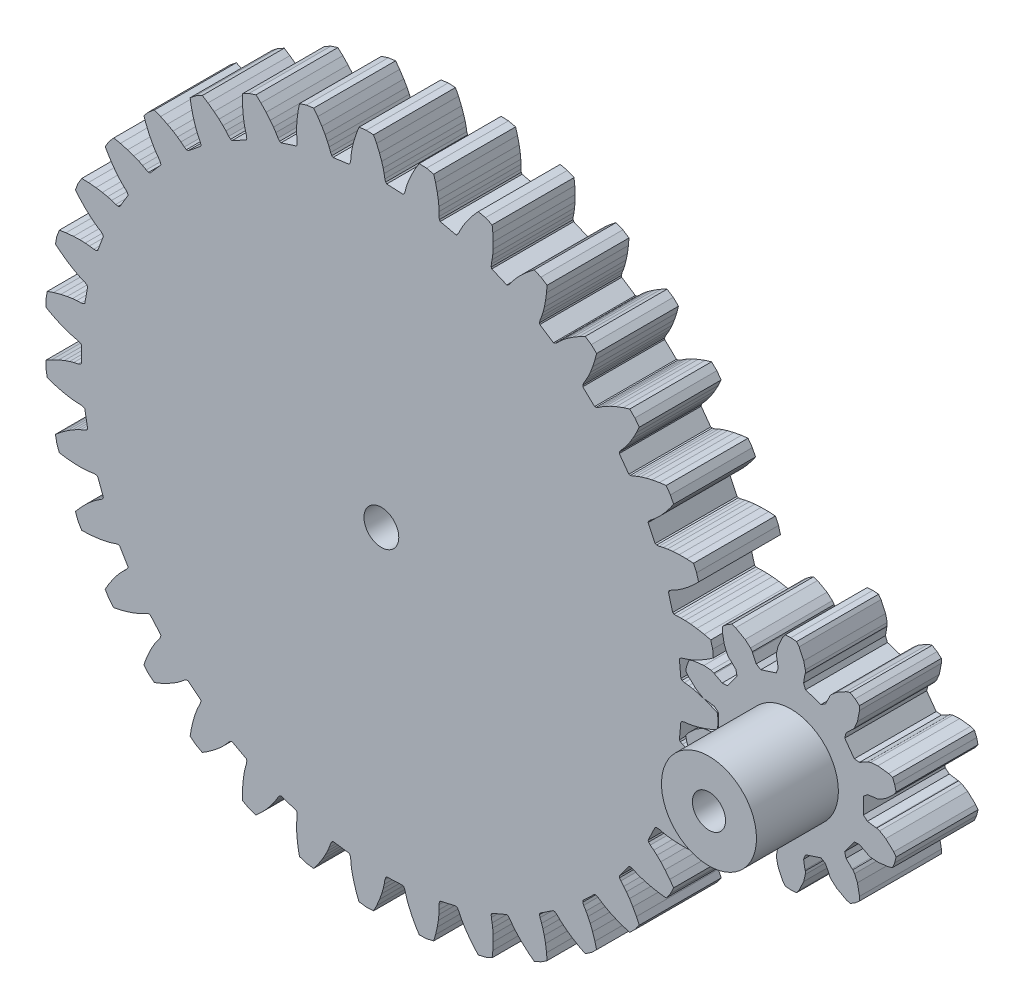
SolidWorks part; units mm, degrees
ref_plane "Front Plane" through (0, 0, 0) normal (0, 0, 1) x (1, 0, 0)
ref_plane "Top Plane" through (0, 0, 0) normal (0, 1, 0) x (1, 0, 0)
ref_plane "Right Plane" through (0, 0, 0) normal (1, 0, 0) x (0, 0, -1)
sketch "Sketch4" plane through (0, 0, 0) normal (0, 0, 1) x (1, 0, 0)
  line L0 (20.4281, -4.1664) -> (20.5488, -3.7291)
  line L1 (20.5488, -3.7291) -> (20.5895, -3.2772)
  line L2 (20.5895, -3.2772) -> (20.2452, -3.0423)
  line L3 (20.2452, -3.0423) -> (19.8455, -2.8032)
  line L4 (19.8455, -2.8032) -> (19.4917, -2.6194)
  line L5 (19.4917, -2.6194) -> (19.1886, -2.4843)
  line L6 (19.1886, -2.4843) -> (18.9407, -2.3911)
  line L7 (18.9407, -2.3911) -> (18.682, -2.3112)
  line L8 (18.682, -2.3112) -> (18.5457, -2.2427)
  line L9 (18.5457, -2.2427) -> (18.4844, -2.1704)
  line L10 (18.4844, -2.1704) -> (18.5748, -1.165)
  line L11 (18.5748, -1.165) -> (18.6481, -1.1048)
  line L12 (18.6481, -1.1048) -> (18.7945, -1.0617)
  line L13 (18.7945, -1.0617) -> (19.0633, -1.0293)
  line L14 (19.0633, -1.0293) -> (19.3238, -0.9819)
  line L15 (19.3238, -0.9819) -> (19.6461, -0.9031)
  line L16 (19.6461, -0.9031) -> (20.0271, -0.7854)
  line L17 (20.0271, -0.7854) -> (20.4631, -0.6215)
  line L18 (20.4631, -0.6215) -> (20.8438, -0.4518)
  line L19 (20.8438, -0.4518) -> (20.8844, 0)
  line L20 (20.8844, 0) -> (20.8438, 0.4518)
  line L21 (20.8438, 0.4518) -> (20.4631, 0.6215)
  line L22 (20.4631, 0.6215) -> (20.0271, 0.7854)
  line L23 (20.0271, 0.7854) -> (19.6461, 0.9031)
  line L24 (19.6461, 0.9031) -> (19.3238, 0.9819)
  line L25 (19.3238, 0.9819) -> (19.0633, 1.0293)
  line L26 (19.0633, 1.0293) -> (18.7945, 1.0617)
  line L27 (18.7945, 1.0617) -> (18.6481, 1.1048)
  line L28 (18.6481, 1.1048) -> (18.5748, 1.165)
  line L29 (18.5748, 1.165) -> (18.4844, 2.1704)
  line L30 (18.4844, 2.1704) -> (18.5457, 2.2427)
  line L31 (18.5457, 2.2427) -> (18.682, 2.3112)
  line L32 (18.682, 2.3112) -> (18.9407, 2.3911)
  line L33 (18.9407, 2.3911) -> (19.1886, 2.4843)
  line L34 (19.1886, 2.4843) -> (19.4917, 2.6194)
  line L35 (19.4917, 2.6194) -> (19.8455, 2.8032)
  line L36 (19.8455, 2.8032) -> (20.2452, 3.0423)
  line L37 (20.2452, 3.0423) -> (20.5895, 3.2772)
  line L38 (20.5895, 3.2772) -> (20.5488, 3.7291)
  line L39 (20.5488, 3.7291) -> (20.4281, 4.1664)
  line L40 (20.4281, 4.1664) -> (20.0232, 4.2654)
  line L41 (20.0232, 4.2654) -> (19.565, 4.3487)
  line L42 (19.565, 4.3487) -> (19.1692, 4.3965)
  line L43 (19.1692, 4.3965) -> (18.838, 4.4165)
  line L44 (18.838, 4.4165) -> (18.5731, 4.4166)
  line L45 (18.5731, 4.4166) -> (18.3029, 4.4005)
  line L46 (18.3029, 4.4005) -> (18.1512, 4.4168)
  line L47 (18.1512, 4.4168) -> (18.0683, 4.4629)
  line L48 (18.0683, 4.4629) -> (17.7998, 5.436)
  line L49 (17.7998, 5.436) -> (17.8472, 5.5181)
  line L50 (17.8472, 5.5181) -> (17.9691, 5.6099)
  line L51 (17.9691, 5.6099) -> (18.2093, 5.7347)
  line L52 (18.2093, 5.7347) -> (18.4366, 5.8706)
  line L53 (18.4366, 5.8706) -> (18.7107, 6.0577)
  line L54 (18.7107, 6.0577) -> (19.026, 6.3017)
  line L55 (19.026, 6.3017) -> (19.3766, 6.6083)
  line L56 (19.3766, 6.6083) -> (19.6734, 6.9009)
  line L57 (19.6734, 6.9009) -> (19.5527, 7.3383)
  line L58 (19.5527, 7.3383) -> (19.3559, 7.747)
  line L59 (19.3559, 7.747) -> (18.9398, 7.7721)
  line L60 (18.9398, 7.7721) -> (18.4741, 7.7723)
  line L61 (18.4741, 7.7723) -> (18.0761, 7.7486)
  line L62 (18.0761, 7.7486) -> (17.7466, 7.7092)
  line L63 (17.7466, 7.7092) -> (17.486, 7.662)
  line L64 (17.486, 7.662) -> (17.223, 7.5979)
  line L65 (17.223, 7.5979) -> (17.0708, 7.5868)
  line L66 (17.0708, 7.5868) -> (16.9811, 7.6174)
  line L67 (16.9811, 7.6174) -> (16.5431, 8.5269)
  line L68 (16.5431, 8.5269) -> (16.5751, 8.6162)
  line L69 (16.5751, 8.6162) -> (16.6786, 8.7282)
  line L70 (16.6786, 8.7282) -> (16.8927, 8.894)
  line L71 (16.8927, 8.894) -> (17.0921, 9.0683)
  line L72 (17.0921, 9.0683) -> (17.3284, 9.3012)
  line L73 (17.3284, 9.3012) -> (17.5951, 9.5977)
  line L74 (17.5951, 9.5977) -> (17.8853, 9.9619)
  line L75 (17.8853, 9.9619) -> (18.1251, 10.3029)
  line L76 (18.1251, 10.3029) -> (17.9282, 10.7116)
  line L77 (17.9282, 10.7116) -> (17.6616, 11.0786)
  line L78 (17.6616, 11.0786) -> (17.2477, 11.0291)
  line L79 (17.2477, 11.0291) -> (16.7894, 10.9461)
  line L80 (16.7894, 10.9461) -> (16.402, 10.8517)
  line L81 (16.402, 10.8517) -> (16.0849, 10.7541)
  line L82 (16.0849, 10.7541) -> (15.8369, 10.6611)
  line L83 (15.8369, 10.6611) -> (15.5895, 10.5511)
  line L84 (15.5895, 10.5511) -> (15.4418, 10.513)
  line L85 (15.4418, 10.513) -> (15.348, 10.5271)
  line L86 (15.348, 10.5271) -> (14.7547, 11.3438)
  line L87 (14.7547, 11.3438) -> (14.7703, 11.4373)
  line L88 (14.7703, 11.4373) -> (14.8521, 11.5661)
  line L89 (14.8521, 11.5661) -> (15.0332, 11.7673)
  line L90 (15.0332, 11.7673) -> (15.1982, 11.9745)
  line L91 (15.1982, 11.9745) -> (15.3891, 12.2459)
  line L92 (15.3891, 12.2459) -> (15.5986, 12.5852)
  line L93 (15.5986, 12.5852) -> (15.8191, 12.9954)
  line L94 (15.8191, 12.9954) -> (15.9941, 13.3737)
  line L95 (15.9941, 13.3737) -> (15.7275, 13.7407)
  line L96 (15.7275, 13.7407) -> (15.3996, 14.0542)
  line L97 (15.3996, 14.0542) -> (15.0012, 13.9315)
  line L98 (15.0012, 13.9315) -> (14.5651, 13.7681)
  line L99 (14.5651, 13.7681) -> (14.2008, 13.606)
  line L100 (14.2008, 13.606) -> (13.9062, 13.4533)
  line L101 (13.9062, 13.4533) -> (13.6788, 13.3176)
  line L102 (13.6788, 13.3176) -> (13.455, 13.1652)
  line L103 (13.455, 13.1652) -> (13.3165, 13.1013)
  line L104 (13.3165, 13.1013) -> (13.2217, 13.0984)
  line L105 (13.2217, 13.0984) -> (12.4921, 13.796)
  line L106 (12.4921, 13.796) -> (12.4907, 13.8909)
  line L107 (12.4907, 13.8909) -> (12.5482, 14.0321)
  line L108 (12.5482, 14.0321) -> (12.6905, 14.2625)
  line L109 (12.6905, 14.2625) -> (12.8159, 14.4958)
  line L110 (12.8159, 14.4958) -> (12.9552, 14.7969)
  line L111 (12.9552, 14.7969) -> (13.1007, 15.1682)
  line L112 (13.1007, 15.1682) -> (13.2445, 15.6111)
  line L113 (13.2445, 15.6111) -> (13.3491, 16.0146)
  line L114 (13.3491, 16.0146) -> (13.0212, 16.3281)
  line L115 (13.0212, 16.3281) -> (12.6426, 16.578)
  line L116 (12.6426, 16.578) -> (12.2726, 16.3862)
  line L117 (12.2726, 16.3862) -> (11.8727, 16.1475)
  line L118 (11.8727, 16.1475) -> (11.5431, 15.923)
  line L119 (11.5431, 15.923) -> (11.2805, 15.7202)
  line L120 (11.2805, 15.7202) -> (11.081, 15.546)
  line L121 (11.081, 15.546) -> (10.8881, 15.3561)
  line L122 (10.8881, 15.3561) -> (10.7632, 15.2685)
  line L123 (10.7632, 15.2685) -> (10.6704, 15.2488)
  line L124 (10.6704, 15.2488) -> (9.8279, 15.8049)
  line L125 (9.8279, 15.8049) -> (9.8096, 15.8979)
  line L126 (9.8096, 15.8979) -> (9.841, 16.0472)
  line L127 (9.841, 16.0472) -> (9.9399, 16.2993)
  line L128 (9.9399, 16.2993) -> (10.0216, 16.5512)
  line L129 (10.0216, 16.5512) -> (10.1049, 16.8724)
  line L130 (10.1049, 16.8724) -> (10.1818, 17.2636)
  line L131 (10.1818, 17.2636) -> (10.2441, 17.7251)
  line L132 (10.2441, 17.7251) -> (10.2751, 18.1408)
  line L133 (10.2751, 18.1408) -> (9.8965, 18.3907)
  line L134 (9.8965, 18.3907) -> (9.4793, 18.5691)
  line L135 (9.4793, 18.5691) -> (9.1495, 18.3142)
  line L136 (9.1495, 18.3142) -> (8.7986, 18.008)
  line L137 (8.7986, 18.008) -> (8.5144, 17.7282)
  line L138 (8.5144, 17.7282) -> (8.2923, 17.4817)
  line L139 (8.2923, 17.4817) -> (8.1271, 17.2748)
  line L140 (8.1271, 17.2748) -> (7.9712, 17.0534)
  line L141 (7.9712, 17.0534) -> (7.8639, 16.945)
  line L142 (7.8639, 16.945) -> (7.7762, 16.909)
  line L143 (7.7762, 16.909) -> (6.8479, 17.3057)
  line L144 (6.8479, 17.3057) -> (6.8133, 17.394)
  line L145 (6.8133, 17.394) -> (6.8176, 17.5465)
  line L146 (6.8176, 17.5465) -> (6.8698, 17.8122)
  line L147 (6.8698, 17.8122) -> (6.9052, 18.0746)
  line L148 (6.9052, 18.0746) -> (6.9299, 18.4055)
  line L149 (6.9299, 18.4055) -> (6.9357, 18.8042)
  line L150 (6.9357, 18.8042) -> (6.9146, 19.2695)
  line L151 (6.9146, 19.2695) -> (6.8708, 19.684)
  line L152 (6.8708, 19.684) -> (6.4536, 19.8623)
  line L153 (6.4536, 19.8623) -> (6.0114, 19.9632)
  line L154 (6.0114, 19.9632) -> (5.7323, 19.6536)
  line L155 (5.7323, 19.6536) -> (5.4418, 19.2896)
  line L156 (5.4418, 19.2896) -> (5.2121, 18.9636)
  line L157 (5.2121, 18.9636) -> (5.0376, 18.6815)
  line L158 (5.0376, 18.6815) -> (4.912, 18.4483)
  line L159 (4.912, 18.4483) -> (4.7981, 18.2027)
  line L160 (4.7981, 18.2027) -> (4.7119, 18.0768)
  line L161 (4.7119, 18.0768) -> (4.632, 18.0257)
  line L162 (4.632, 18.0257) -> (3.6478, 18.2504)
  line L163 (3.6478, 18.2504) -> (3.598, 18.3311)
  line L164 (3.598, 18.3311) -> (3.5749, 18.4819)
  line L165 (3.5749, 18.4819) -> (3.5789, 18.7526)
  line L166 (3.5789, 18.7526) -> (3.5669, 19.0171)
  line L167 (3.5669, 19.0171) -> (3.5321, 19.3471)
  line L168 (3.5321, 19.3471) -> (3.4666, 19.7404)
  line L169 (3.4666, 19.7404) -> (3.3627, 20.1944)
  line L170 (3.3627, 20.1944) -> (3.2457, 20.5945)
  line L171 (3.2457, 20.5945) -> (2.8034, 20.6954)
  line L172 (2.8034, 20.6954) -> (2.3502, 20.7158)
  line L173 (2.3502, 20.7158) -> (2.1309, 20.3613)
  line L174 (2.1309, 20.3613) -> (1.91, 19.9513)
  line L175 (1.91, 19.9513) -> (1.7423, 19.5895)
  line L176 (1.7423, 19.5895) -> (1.6209, 19.2807)
  line L177 (1.6209, 19.2807) -> (1.539, 19.0289)
  line L178 (1.539, 19.0289) -> (1.4707, 18.7669)
  line L179 (1.4707, 18.7669) -> (1.4084, 18.6277)
  line L180 (1.4084, 18.6277) -> (1.3389, 18.5631)
  line L181 (1.3389, 18.5631) -> (0.3305, 18.6084)
  line L182 (0.3305, 18.6084) -> (0.267, 18.6789)
  line L183 (0.267, 18.6789) -> (0.2174, 18.8232)
  line L184 (0.2174, 18.8232) -> (0.173, 19.0902)
  line L185 (0.173, 19.0902) -> (0.1139, 19.3484)
  line L186 (0.1139, 19.3484) -> (0.0207, 19.6669)
  line L187 (0.0207, 19.6669) -> (-0.1139, 20.0422)
  line L188 (-0.1139, 20.0422) -> (-0.2972, 20.4703)
  line L189 (-0.2972, 20.4703) -> (-0.4838, 20.8431)
  line L190 (-0.4838, 20.8431) -> (-0.937, 20.8634)
  line L191 (-0.937, 20.8634) -> (-1.3865, 20.8025)
  line L192 (-1.3865, 20.8025) -> (-1.539, 20.4146)
  line L193 (-1.539, 20.4146) -> (-1.6831, 19.9717)
  line L194 (-1.6831, 19.9717) -> (-1.7836, 19.5858)
  line L195 (-1.7836, 19.5858) -> (-1.8478, 19.2603)
  line L196 (-1.8478, 19.2603) -> (-1.8835, 18.9979)
  line L197 (-1.8835, 18.9979) -> (-1.9039, 18.7279)
  line L198 (-1.9039, 18.7279) -> (-1.9403, 18.5798)
  line L199 (-1.9403, 18.5798) -> (-1.9972, 18.5039)
  line L200 (-1.9972, 18.5039) -> (-2.9975, 18.3684)
  line L201 (-2.9975, 18.3684) -> (-3.0725, 18.4264)
  line L202 (-3.0725, 18.4264) -> (-3.1471, 18.5595)
  line L203 (-3.1471, 18.5595) -> (-3.2385, 18.8143)
  line L204 (-3.2385, 18.8143) -> (-3.3427, 19.0578)
  line L205 (-3.3427, 19.0578) -> (-3.4912, 19.3545)
  line L206 (-3.4912, 19.3545) -> (-3.6908, 19.6998)
  line L207 (-3.6908, 19.6998) -> (-3.9475, 20.0883)
  line L208 (-3.9475, 20.0883) -> (-4.1977, 20.4217)
  line L209 (-4.1977, 20.4217) -> (-4.6472, 20.3608)
  line L210 (-4.6472, 20.3608) -> (-5.0787, 20.2206)
  line L211 (-5.0787, 20.2206) -> (-5.1594, 19.8117)
  line L212 (-5.1594, 19.8117) -> (-5.2221, 19.3502)
  line L213 (-5.2221, 19.3502) -> (-5.2521, 18.9526)
  line L214 (-5.2521, 18.9526) -> (-5.2572, 18.6208)
  line L215 (-5.2572, 18.6208) -> (-5.2454, 18.3563)
  line L216 (-5.2454, 18.3563) -> (-5.2173, 18.087)
  line L217 (-5.2173, 18.087) -> (-5.2267, 17.9347)
  line L218 (-5.2267, 17.9347) -> (-5.2691, 17.8499)
  line L219 (-5.2691, 17.8499) -> (-6.2291, 17.538)
  line L220 (-6.2291, 17.538) -> (-6.3133, 17.5817)
  line L221 (-6.3133, 17.5817) -> (-6.4104, 17.6993)
  line L222 (-6.4104, 17.6993) -> (-6.5459, 17.9337)
  line L223 (-6.5459, 17.9337) -> (-6.6919, 18.1547)
  line L224 (-6.6919, 18.1547) -> (-6.891, 18.4201)
  line L225 (-6.891, 18.4201) -> (-7.149, 18.7242)
  line L226 (-7.149, 18.7242) -> (-7.471, 19.0606)
  line L227 (-7.471, 19.0606) -> (-7.7766, 19.344)
  line L228 (-7.7766, 19.344) -> (-8.2081, 19.2038)
  line L229 (-8.2081, 19.2038) -> (-8.6076, 18.9888)
  line L230 (-8.6076, 18.9888) -> (-8.614, 18.5721)
  line L231 (-8.614, 18.5721) -> (-8.5933, 18.1068)
  line L232 (-8.5933, 18.1068) -> (-8.5518, 17.7102)
  line L233 (-8.5518, 17.7102) -> (-8.4976, 17.3829)
  line L234 (-8.4976, 17.3829) -> (-8.4388, 17.1247)
  line L235 (-8.4388, 17.1247) -> (-8.363, 16.8648)
  line L236 (-8.363, 16.8648) -> (-8.3451, 16.7133)
  line L237 (-8.3451, 16.7133) -> (-8.3716, 16.6222)
  line L238 (-8.3716, 16.6222) -> (-9.2606, 16.1439)
  line L239 (-9.2606, 16.1439) -> (-9.3512, 16.1719)
  line L240 (-9.3512, 16.1719) -> (-9.4677, 16.2703)
  line L241 (-9.4677, 16.2703) -> (-9.6429, 16.4767)
  line L242 (-9.6429, 16.4767) -> (-9.826, 16.6681)
  line L243 (-9.826, 16.6681) -> (-10.0693, 16.8936)
  line L244 (-10.0693, 16.8936) -> (-10.3774, 17.1468)
  line L245 (-10.3774, 17.1468) -> (-10.7543, 17.4203)
  line L246 (-10.7543, 17.4203) -> (-11.1057, 17.6446)
  line L247 (-11.1057, 17.6446) -> (-11.5052, 17.4296)
  line L248 (-11.5052, 17.4296) -> (-11.8599, 17.1467)
  line L249 (-11.8599, 17.1467) -> (-11.7918, 16.7355)
  line L250 (-11.7918, 16.7355) -> (-11.6883, 16.2814)
  line L251 (-11.6883, 16.2814) -> (-11.5767, 15.8986)
  line L252 (-11.5767, 15.8986) -> (-11.4649, 15.5862)
  line L253 (-11.4649, 15.5862) -> (-11.3609, 15.3427)
  line L254 (-11.3609, 15.3427) -> (-11.2399, 15.1005)
  line L255 (-11.2399, 15.1005) -> (-11.1952, 14.9546)
  line L256 (-11.1952, 14.9546) -> (-11.2051, 14.8603)
  line L257 (-11.2051, 14.8603) -> (-11.9943, 14.2309)
  line L258 (-11.9943, 14.2309) -> (-12.0885, 14.2422)
  line L259 (-12.0885, 14.2422) -> (-12.2208, 14.3183)
  line L260 (-12.2208, 14.3183) -> (-12.43, 14.4901)
  line L261 (-12.43, 14.4901) -> (-12.6443, 14.6457)
  line L262 (-12.6443, 14.6457) -> (-12.924, 14.8242)
  line L263 (-12.924, 14.8242) -> (-13.2723, 15.0182)
  line L264 (-13.2723, 15.0182) -> (-13.692, 15.2201)
  line L265 (-13.692, 15.2201) -> (-14.0778, 15.378)
  line L266 (-14.0778, 15.378) -> (-14.4325, 15.0952)
  line L267 (-14.4325, 15.0952) -> (-14.7309, 14.7535)
  line L268 (-14.7309, 14.7535) -> (-14.5905, 14.3611)
  line L269 (-14.5905, 14.3611) -> (-14.4077, 13.9328)
  line L270 (-14.4077, 13.9328) -> (-14.2294, 13.576)
  line L271 (-14.2294, 13.576) -> (-14.0637, 13.2886)
  line L272 (-14.0637, 13.2886) -> (-13.9179, 13.0675)
  line L273 (-13.9179, 13.0675) -> (-13.7556, 12.8508)
  line L274 (-13.7556, 12.8508) -> (-13.6856, 12.7153)
  line L275 (-13.6856, 12.7153) -> (-13.6784, 12.6207)
  line L276 (-13.6784, 12.6207) -> (-14.3426, 11.8605)
  line L277 (-14.3426, 11.8605) -> (-14.4373, 11.8549)
  line L278 (-14.4373, 11.8549) -> (-14.581, 11.9061)
  line L279 (-14.581, 11.9061) -> (-14.8175, 12.0378)
  line L280 (-14.8175, 12.0378) -> (-15.0562, 12.1526)
  line L281 (-15.0562, 12.1526) -> (-15.3632, 12.2783)
  line L282 (-15.3632, 12.2783) -> (-15.7406, 12.407)
  line L283 (-15.7406, 12.407) -> (-16.1896, 12.5307)
  line L284 (-16.1896, 12.5307) -> (-16.5974, 12.6172)
  line L285 (-16.5974, 12.6172) -> (-16.8959, 12.2756)
  line L286 (-16.8959, 12.2756) -> (-17.1286, 11.8861)
  line L287 (-17.1286, 11.8861) -> (-16.9203, 11.525)
  line L288 (-16.9203, 11.525) -> (-16.6639, 11.1363)
  line L289 (-16.6639, 11.1363) -> (-16.4249, 10.8171)
  line L290 (-16.4249, 10.8171) -> (-16.2104, 10.5639)
  line L291 (-16.2104, 10.5639) -> (-16.0275, 10.3724)
  line L292 (-16.0275, 10.3724) -> (-15.8291, 10.1882)
  line L293 (-15.8291, 10.1882) -> (-15.736, 10.0673)
  line L294 (-15.736, 10.0673) -> (-15.7121, 9.9755)
  line L295 (-15.7121, 9.9755) -> (-16.2299, 9.1089)
  line L296 (-16.2299, 9.1089) -> (-16.322, 9.0865)
  line L297 (-16.322, 9.0865) -> (-16.4726, 9.1112)
  line L298 (-16.4726, 9.1112) -> (-16.7288, 9.1986)
  line L299 (-16.7288, 9.1986) -> (-16.9841, 9.2689)
  line L300 (-16.9841, 9.2689) -> (-17.3087, 9.3378)
  line L301 (-17.3087, 9.3378) -> (-17.703, 9.397)
  line L302 (-17.703, 9.397) -> (-18.1669, 9.4386)
  line L303 (-18.1669, 9.4386) -> (-18.5835, 9.4509)
  line L304 (-18.5835, 9.4509) -> (-18.8162, 9.0614)
  line L305 (-18.8162, 9.0614) -> (-18.9756, 8.6367)
  line L306 (-18.9756, 8.6367) -> (-18.7063, 8.3186)
  line L307 (-18.7063, 8.3186) -> (-18.3846, 7.9818)
  line L308 (-18.3846, 7.9818) -> (-18.0924, 7.7105)
  line L309 (-18.0924, 7.7105) -> (-17.8362, 7.4997)
  line L310 (-17.8362, 7.4997) -> (-17.622, 7.3439)
  line L311 (-17.622, 7.3439) -> (-17.3939, 7.198)
  line L312 (-17.3939, 7.198) -> (-17.2807, 7.0957)
  line L313 (-17.2807, 7.0957) -> (-17.2408, 7.0097)
  line L314 (-17.2408, 7.0097) -> (-17.5955, 6.0646)
  line L315 (-17.5955, 6.0646) -> (-17.6822, 6.0261)
  line L316 (-17.6822, 6.0261) -> (-17.8347, 6.0235)
  line L317 (-17.8347, 6.0235) -> (-18.1024, 6.0637)
  line L318 (-18.1024, 6.0637) -> (-18.3662, 6.0873)
  line L319 (-18.3662, 6.0873) -> (-18.6979, 6.0971)
  line L320 (-18.6979, 6.0971) -> (-19.0965, 6.085)
  line L321 (-19.0965, 6.085) -> (-19.5603, 6.0431)
  line L322 (-19.5603, 6.0431) -> (-19.9724, 5.9808)
  line L323 (-19.9724, 5.9808) -> (-20.1318, 5.556)
  line L324 (-20.1318, 5.556) -> (-20.2128, 5.1097)
  line L325 (-20.2128, 5.1097) -> (-19.891, 4.8448)
  line L326 (-19.891, 4.8448) -> (-19.5143, 4.5709)
  line L327 (-19.5143, 4.5709) -> (-19.1784, 4.3561)
  line L328 (-19.1784, 4.3561) -> (-18.8887, 4.1944)
  line L329 (-18.8887, 4.1944) -> (-18.6501, 4.0793)
  line L330 (-18.6501, 4.0793) -> (-18.3996, 3.9766)
  line L331 (-18.3996, 3.9766) -> (-18.27, 3.8961)
  line L332 (-18.27, 3.8961) -> (-18.2154, 3.8186)
  line L333 (-18.2154, 3.8186) -> (-18.3956, 2.8253)
  line L334 (-18.3956, 2.8253) -> (-18.474, 2.7719)
  line L335 (-18.474, 2.7719) -> (-18.6236, 2.7422)
  line L336 (-18.6236, 2.7422) -> (-18.8942, 2.7339)
  line L337 (-18.8942, 2.7339) -> (-19.158, 2.7101)
  line L338 (-19.158, 2.7101) -> (-19.4861, 2.6605)
  line L339 (-19.4861, 2.6605) -> (-19.8761, 2.5774)
  line L340 (-19.8761, 2.5774) -> (-20.325, 2.4533)
  line L341 (-20.325, 2.4533) -> (-20.7194, 2.3184)
  line L342 (-20.7194, 2.3184) -> (-20.8004, 1.8721)
  line L343 (-20.8004, 1.8721) -> (-20.8004, 1.4184)
  line L344 (-20.8004, 1.4184) -> (-20.4364, 1.2153)
  line L345 (-20.4364, 1.2153) -> (-20.0169, 1.013)
  line L346 (-20.0169, 1.013) -> (-19.648, 0.8616)
  line L347 (-19.648, 0.8616) -> (-19.334, 0.7543)
  line L348 (-19.334, 0.7543) -> (-19.0788, 0.6837)
  line L349 (-19.0788, 0.6837) -> (-18.814, 0.6273)
  line L350 (-18.814, 0.6273) -> (-18.6721, 0.5713)
  line L351 (-18.6721, 0.5713) -> (-18.6045, 0.5047)
  line L352 (-18.6045, 0.5047) -> (-18.6045, -0.5047)
  line L353 (-18.6045, -0.5047) -> (-18.6721, -0.5713)
  line L354 (-18.6721, -0.5713) -> (-18.814, -0.6273)
  line L355 (-18.814, -0.6273) -> (-19.0788, -0.6837)
  line L356 (-19.0788, -0.6837) -> (-19.334, -0.7543)
  line L357 (-19.334, -0.7543) -> (-19.648, -0.8616)
  line L358 (-19.648, -0.8616) -> (-20.0169, -1.013)
  line L359 (-20.0169, -1.013) -> (-20.4364, -1.2153)
  line L360 (-20.4364, -1.2153) -> (-20.8004, -1.4184)
  line L361 (-20.8004, -1.4184) -> (-20.8004, -1.8721)
  line L362 (-20.8004, -1.8721) -> (-20.7194, -2.3184)
  line L363 (-20.7194, -2.3184) -> (-20.325, -2.4533)
  line L364 (-20.325, -2.4533) -> (-19.8761, -2.5774)
  line L365 (-19.8761, -2.5774) -> (-19.4861, -2.6605)
  line L366 (-19.4861, -2.6605) -> (-19.158, -2.7101)
  line L367 (-19.158, -2.7101) -> (-18.8942, -2.7339)
  line L368 (-18.8942, -2.7339) -> (-18.6236, -2.7422)
  line L369 (-18.6236, -2.7422) -> (-18.474, -2.7719)
  line L370 (-18.474, -2.7719) -> (-18.3956, -2.8253)
  line L371 (-18.3956, -2.8253) -> (-18.2154, -3.8186)
  line L372 (-18.2154, -3.8186) -> (-18.27, -3.8961)
  line L373 (-18.27, -3.8961) -> (-18.3996, -3.9766)
  line L374 (-18.3996, -3.9766) -> (-18.6501, -4.0793)
  line L375 (-18.6501, -4.0793) -> (-18.8887, -4.1944)
  line L376 (-18.8887, -4.1944) -> (-19.1784, -4.3561)
  line L377 (-19.1784, -4.3561) -> (-19.5143, -4.5709)
  line L378 (-19.5143, -4.5709) -> (-19.891, -4.8448)
  line L379 (-19.891, -4.8448) -> (-20.2128, -5.1097)
  line L380 (-20.2128, -5.1097) -> (-20.1318, -5.556)
  line L381 (-20.1318, -5.556) -> (-19.9724, -5.9808)
  line L382 (-19.9724, -5.9808) -> (-19.5603, -6.0431)
  line L383 (-19.5603, -6.0431) -> (-19.0965, -6.085)
  line L384 (-19.0965, -6.085) -> (-18.6979, -6.0971)
  line L385 (-18.6979, -6.0971) -> (-18.3662, -6.0873)
  line L386 (-18.3662, -6.0873) -> (-18.1024, -6.0637)
  line L387 (-18.1024, -6.0637) -> (-17.8347, -6.0235)
  line L388 (-17.8347, -6.0235) -> (-17.6822, -6.0261)
  line L389 (-17.6822, -6.0261) -> (-17.5955, -6.0646)
  line L390 (-17.5955, -6.0646) -> (-17.2408, -7.0097)
  line L391 (-17.2408, -7.0097) -> (-17.2807, -7.0957)
  line L392 (-17.2807, -7.0957) -> (-17.3939, -7.198)
  line L393 (-17.3939, -7.198) -> (-17.622, -7.3439)
  line L394 (-17.622, -7.3439) -> (-17.8362, -7.4997)
  line L395 (-17.8362, -7.4997) -> (-18.0924, -7.7105)
  line L396 (-18.0924, -7.7105) -> (-18.3846, -7.9818)
  line L397 (-18.3846, -7.9818) -> (-18.7063, -8.3186)
  line L398 (-18.7063, -8.3186) -> (-18.9756, -8.6367)
  line L399 (-18.9756, -8.6367) -> (-18.8162, -9.0614)
  line L400 (-18.8162, -9.0614) -> (-18.5835, -9.4509)
  line L401 (-18.5835, -9.4509) -> (-18.1669, -9.4386)
  line L402 (-18.1669, -9.4386) -> (-17.703, -9.397)
  line L403 (-17.703, -9.397) -> (-17.3087, -9.3378)
  line L404 (-17.3087, -9.3378) -> (-16.9841, -9.2689)
  line L405 (-16.9841, -9.2689) -> (-16.7288, -9.1986)
  line L406 (-16.7288, -9.1986) -> (-16.4726, -9.1112)
  line L407 (-16.4726, -9.1112) -> (-16.322, -9.0865)
  line L408 (-16.322, -9.0865) -> (-16.2299, -9.1089)
  line L409 (-16.2299, -9.1089) -> (-15.7121, -9.9755)
  line L410 (-15.7121, -9.9755) -> (-15.736, -10.0673)
  line L411 (-15.736, -10.0673) -> (-15.8291, -10.1882)
  line L412 (-15.8291, -10.1882) -> (-16.0275, -10.3724)
  line L413 (-16.0275, -10.3724) -> (-16.2104, -10.5639)
  line L414 (-16.2104, -10.5639) -> (-16.4249, -10.8171)
  line L415 (-16.4249, -10.8171) -> (-16.6639, -11.1363)
  line L416 (-16.6639, -11.1363) -> (-16.9203, -11.525)
  line L417 (-16.9203, -11.525) -> (-17.1286, -11.8861)
  line L418 (-17.1286, -11.8861) -> (-16.8959, -12.2756)
  line L419 (-16.8959, -12.2756) -> (-16.5974, -12.6172)
  line L420 (-16.5974, -12.6172) -> (-16.1896, -12.5307)
  line L421 (-16.1896, -12.5307) -> (-15.7406, -12.407)
  line L422 (-15.7406, -12.407) -> (-15.3632, -12.2783)
  line L423 (-15.3632, -12.2783) -> (-15.0562, -12.1526)
  line L424 (-15.0562, -12.1526) -> (-14.8175, -12.0378)
  line L425 (-14.8175, -12.0378) -> (-14.581, -11.9061)
  line L426 (-14.581, -11.9061) -> (-14.4373, -11.8549)
  line L427 (-14.4373, -11.8549) -> (-14.3426, -11.8605)
  line L428 (-14.3426, -11.8605) -> (-13.6784, -12.6207)
  line L429 (-13.6784, -12.6207) -> (-13.6856, -12.7153)
  line L430 (-13.6856, -12.7153) -> (-13.7556, -12.8508)
  line L431 (-13.7556, -12.8508) -> (-13.9179, -13.0675)
  line L432 (-13.9179, -13.0675) -> (-14.0637, -13.2886)
  line L433 (-14.0637, -13.2886) -> (-14.2294, -13.576)
  line L434 (-14.2294, -13.576) -> (-14.4077, -13.9328)
  line L435 (-14.4077, -13.9328) -> (-14.5905, -14.3611)
  line L436 (-14.5905, -14.3611) -> (-14.7309, -14.7535)
  line L437 (-14.7309, -14.7535) -> (-14.4325, -15.0952)
  line L438 (-14.4325, -15.0952) -> (-14.0778, -15.378)
  line L439 (-14.0778, -15.378) -> (-13.692, -15.2201)
  line L440 (-13.692, -15.2201) -> (-13.2723, -15.0182)
  line L441 (-13.2723, -15.0182) -> (-12.924, -14.8242)
  line L442 (-12.924, -14.8242) -> (-12.6443, -14.6457)
  line L443 (-12.6443, -14.6457) -> (-12.43, -14.4901)
  line L444 (-12.43, -14.4901) -> (-12.2208, -14.3183)
  line L445 (-12.2208, -14.3183) -> (-12.0885, -14.2422)
  line L446 (-12.0885, -14.2422) -> (-11.9943, -14.2309)
  line L447 (-11.9943, -14.2309) -> (-11.2051, -14.8603)
  line L448 (-11.2051, -14.8603) -> (-11.1952, -14.9546)
  line L449 (-11.1952, -14.9546) -> (-11.2399, -15.1005)
  line L450 (-11.2399, -15.1005) -> (-11.3609, -15.3427)
  line L451 (-11.3609, -15.3427) -> (-11.4649, -15.5862)
  line L452 (-11.4649, -15.5862) -> (-11.5767, -15.8986)
  line L453 (-11.5767, -15.8986) -> (-11.6883, -16.2814)
  line L454 (-11.6883, -16.2814) -> (-11.7918, -16.7355)
  line L455 (-11.7918, -16.7355) -> (-11.8599, -17.1467)
  line L456 (-11.8599, -17.1467) -> (-11.5052, -17.4296)
  line L457 (-11.5052, -17.4296) -> (-11.1057, -17.6446)
  line L458 (-11.1057, -17.6446) -> (-10.7543, -17.4203)
  line L459 (-10.7543, -17.4203) -> (-10.3774, -17.1468)
  line L460 (-10.3774, -17.1468) -> (-10.0693, -16.8936)
  line L461 (-10.0693, -16.8936) -> (-9.826, -16.6681)
  line L462 (-9.826, -16.6681) -> (-9.6429, -16.4767)
  line L463 (-9.6429, -16.4767) -> (-9.4677, -16.2703)
  line L464 (-9.4677, -16.2703) -> (-9.3512, -16.1719)
  line L465 (-9.3512, -16.1719) -> (-9.2606, -16.1439)
  line L466 (-9.2606, -16.1439) -> (-8.3716, -16.6222)
  line L467 (-8.3716, -16.6222) -> (-8.3451, -16.7133)
  line L468 (-8.3451, -16.7133) -> (-8.363, -16.8648)
  line L469 (-8.363, -16.8648) -> (-8.4388, -17.1247)
  line L470 (-8.4388, -17.1247) -> (-8.4976, -17.3829)
  line L471 (-8.4976, -17.3829) -> (-8.5518, -17.7102)
  line L472 (-8.5518, -17.7102) -> (-8.5933, -18.1068)
  line L473 (-8.5933, -18.1068) -> (-8.614, -18.5721)
  line L474 (-8.614, -18.5721) -> (-8.6076, -18.9888)
  line L475 (-8.6076, -18.9888) -> (-8.2081, -19.2038)
  line L476 (-8.2081, -19.2038) -> (-7.7766, -19.344)
  line L477 (-7.7766, -19.344) -> (-7.471, -19.0606)
  line L478 (-7.471, -19.0606) -> (-7.149, -18.7242)
  line L479 (-7.149, -18.7242) -> (-6.891, -18.4201)
  line L480 (-6.891, -18.4201) -> (-6.6919, -18.1547)
  line L481 (-6.6919, -18.1547) -> (-6.5459, -17.9337)
  line L482 (-6.5459, -17.9337) -> (-6.4104, -17.6993)
  line L483 (-6.4104, -17.6993) -> (-6.3133, -17.5817)
  line L484 (-6.3133, -17.5817) -> (-6.2291, -17.538)
  line L485 (-6.2291, -17.538) -> (-5.2691, -17.8499)
  line L486 (-5.2691, -17.8499) -> (-5.2267, -17.9347)
  line L487 (-5.2267, -17.9347) -> (-5.2173, -18.087)
  line L488 (-5.2173, -18.087) -> (-5.2454, -18.3563)
  line L489 (-5.2454, -18.3563) -> (-5.2572, -18.6208)
  line L490 (-5.2572, -18.6208) -> (-5.2521, -18.9526)
  line L491 (-5.2521, -18.9526) -> (-5.2221, -19.3502)
  line L492 (-5.2221, -19.3502) -> (-5.1594, -19.8117)
  line L493 (-5.1594, -19.8117) -> (-5.0787, -20.2206)
  line L494 (-5.0787, -20.2206) -> (-4.6472, -20.3608)
  line L495 (-4.6472, -20.3608) -> (-4.1977, -20.4217)
  line L496 (-4.1977, -20.4217) -> (-3.9475, -20.0883)
  line L497 (-3.9475, -20.0883) -> (-3.6908, -19.6998)
  line L498 (-3.6908, -19.6998) -> (-3.4912, -19.3545)
  line L499 (-3.4912, -19.3545) -> (-3.3427, -19.0578)
  line L500 (-3.3427, -19.0578) -> (-3.2385, -18.8143)
  line L501 (-3.2385, -18.8143) -> (-3.1471, -18.5595)
  line L502 (-3.1471, -18.5595) -> (-3.0725, -18.4264)
  line L503 (-3.0725, -18.4264) -> (-2.9975, -18.3684)
  line L504 (-2.9975, -18.3684) -> (-1.9972, -18.5039)
  line L505 (-1.9972, -18.5039) -> (-1.9403, -18.5798)
  line L506 (-1.9403, -18.5798) -> (-1.9039, -18.7279)
  line L507 (-1.9039, -18.7279) -> (-1.8835, -18.9979)
  line L508 (-1.8835, -18.9979) -> (-1.8478, -19.2603)
  line L509 (-1.8478, -19.2603) -> (-1.7836, -19.5858)
  line L510 (-1.7836, -19.5858) -> (-1.6831, -19.9717)
  line L511 (-1.6831, -19.9717) -> (-1.539, -20.4146)
  line L512 (-1.539, -20.4146) -> (-1.3865, -20.8025)
  line L513 (-1.3865, -20.8025) -> (-0.937, -20.8634)
  line L514 (-0.937, -20.8634) -> (-0.4838, -20.8431)
  line L515 (-0.4838, -20.8431) -> (-0.2972, -20.4703)
  line L516 (-0.2972, -20.4703) -> (-0.1139, -20.0422)
  line L517 (-0.1139, -20.0422) -> (0.0207, -19.6669)
  line L518 (0.0207, -19.6669) -> (0.1139, -19.3484)
  line L519 (0.1139, -19.3484) -> (0.173, -19.0902)
  line L520 (0.173, -19.0902) -> (0.2174, -18.8232)
  line L521 (0.2174, -18.8232) -> (0.267, -18.6789)
  line L522 (0.267, -18.6789) -> (0.3305, -18.6084)
  line L523 (0.3305, -18.6084) -> (1.3389, -18.5631)
  line L524 (1.3389, -18.5631) -> (1.4084, -18.6277)
  line L525 (1.4084, -18.6277) -> (1.4707, -18.7669)
  line L526 (1.4707, -18.7669) -> (1.539, -19.0289)
  line L527 (1.539, -19.0289) -> (1.6209, -19.2807)
  line L528 (1.6209, -19.2807) -> (1.7423, -19.5895)
  line L529 (1.7423, -19.5895) -> (1.91, -19.9513)
  line L530 (1.91, -19.9513) -> (2.1309, -20.3613)
  line L531 (2.1309, -20.3613) -> (2.3502, -20.7158)
  line L532 (2.3502, -20.7158) -> (2.8034, -20.6954)
  line L533 (2.8034, -20.6954) -> (3.2457, -20.5945)
  line L534 (3.2457, -20.5945) -> (3.3627, -20.1944)
  line L535 (3.3627, -20.1944) -> (3.4666, -19.7404)
  line L536 (3.4666, -19.7404) -> (3.5321, -19.3471)
  line L537 (3.5321, -19.3471) -> (3.5669, -19.0171)
  line L538 (3.5669, -19.0171) -> (3.5789, -18.7526)
  line L539 (3.5789, -18.7526) -> (3.5749, -18.4819)
  line L540 (3.5749, -18.4819) -> (3.598, -18.3311)
  line L541 (3.598, -18.3311) -> (3.6478, -18.2504)
  line L542 (3.6478, -18.2504) -> (4.632, -18.0257)
  line L543 (4.632, -18.0257) -> (4.7119, -18.0768)
  line L544 (4.7119, -18.0768) -> (4.7981, -18.2027)
  line L545 (4.7981, -18.2027) -> (4.912, -18.4483)
  line L546 (4.912, -18.4483) -> (5.0376, -18.6815)
  line L547 (5.0376, -18.6815) -> (5.2121, -18.9636)
  line L548 (5.2121, -18.9636) -> (5.4418, -19.2896)
  line L549 (5.4418, -19.2896) -> (5.7323, -19.6536)
  line L550 (5.7323, -19.6536) -> (6.0114, -19.9632)
  line L551 (6.0114, -19.9632) -> (6.4536, -19.8623)
  line L552 (6.4536, -19.8623) -> (6.8708, -19.684)
  line L553 (6.8708, -19.684) -> (6.9146, -19.2695)
  line L554 (6.9146, -19.2695) -> (6.9357, -18.8042)
  line L555 (6.9357, -18.8042) -> (6.9299, -18.4055)
  line L556 (6.9299, -18.4055) -> (6.9052, -18.0746)
  line L557 (6.9052, -18.0746) -> (6.8698, -17.8122)
  line L558 (6.8698, -17.8122) -> (6.8176, -17.5465)
  line L559 (6.8176, -17.5465) -> (6.8133, -17.394)
  line L560 (6.8133, -17.394) -> (6.8479, -17.3057)
  line L561 (6.8479, -17.3057) -> (7.7762, -16.909)
  line L562 (7.7762, -16.909) -> (7.8639, -16.945)
  line L563 (7.8639, -16.945) -> (7.9712, -17.0534)
  line L564 (7.9712, -17.0534) -> (8.1271, -17.2748)
  line L565 (8.1271, -17.2748) -> (8.2923, -17.4817)
  line L566 (8.2923, -17.4817) -> (8.5144, -17.7282)
  line L567 (8.5144, -17.7282) -> (8.7986, -18.008)
  line L568 (8.7986, -18.008) -> (9.1495, -18.3142)
  line L569 (9.1495, -18.3142) -> (9.4793, -18.5691)
  line L570 (9.4793, -18.5691) -> (9.8965, -18.3907)
  line L571 (9.8965, -18.3907) -> (10.2751, -18.1408)
  line L572 (10.2751, -18.1408) -> (10.2441, -17.7251)
  line L573 (10.2441, -17.7251) -> (10.1818, -17.2636)
  line L574 (10.1818, -17.2636) -> (10.1049, -16.8724)
  line L575 (10.1049, -16.8724) -> (10.0216, -16.5512)
  line L576 (10.0216, -16.5512) -> (9.9399, -16.2993)
  line L577 (9.9399, -16.2993) -> (9.841, -16.0472)
  line L578 (9.841, -16.0472) -> (9.8096, -15.8979)
  line L579 (9.8096, -15.8979) -> (9.8279, -15.8049)
  line L580 (9.8279, -15.8049) -> (10.6704, -15.2488)
  line L581 (10.6704, -15.2488) -> (10.7632, -15.2685)
  line L582 (10.7632, -15.2685) -> (10.8881, -15.3561)
  line L583 (10.8881, -15.3561) -> (11.081, -15.546)
  line L584 (11.081, -15.546) -> (11.2805, -15.7202)
  line L585 (11.2805, -15.7202) -> (11.5431, -15.923)
  line L586 (11.5431, -15.923) -> (11.8727, -16.1475)
  line L587 (11.8727, -16.1475) -> (12.2726, -16.3862)
  line L588 (12.2726, -16.3862) -> (12.6426, -16.578)
  line L589 (12.6426, -16.578) -> (13.0212, -16.3281)
  line L590 (13.0212, -16.3281) -> (13.3491, -16.0146)
  line L591 (13.3491, -16.0146) -> (13.2445, -15.6111)
  line L592 (13.2445, -15.6111) -> (13.1007, -15.1682)
  line L593 (13.1007, -15.1682) -> (12.9552, -14.7969)
  line L594 (12.9552, -14.7969) -> (12.8159, -14.4958)
  line L595 (12.8159, -14.4958) -> (12.6905, -14.2625)
  line L596 (12.6905, -14.2625) -> (12.5482, -14.0321)
  line L597 (12.5482, -14.0321) -> (12.4907, -13.8909)
  line L598 (12.4907, -13.8909) -> (12.4921, -13.796)
  line L599 (12.4921, -13.796) -> (13.2217, -13.0984)
  line L600 (13.2217, -13.0984) -> (13.3165, -13.1013)
  line L601 (13.3165, -13.1013) -> (13.455, -13.1652)
  line L602 (13.455, -13.1652) -> (13.6788, -13.3176)
  line L603 (13.6788, -13.3176) -> (13.9062, -13.4533)
  line L604 (13.9062, -13.4533) -> (14.2008, -13.606)
  line L605 (14.2008, -13.606) -> (14.5651, -13.7681)
  line L606 (14.5651, -13.7681) -> (15.0012, -13.9315)
  line L607 (15.0012, -13.9315) -> (15.3996, -14.0542)
  line L608 (15.3996, -14.0542) -> (15.7275, -13.7407)
  line L609 (15.7275, -13.7407) -> (15.9941, -13.3737)
  line L610 (15.9941, -13.3737) -> (15.8191, -12.9954)
  line L611 (15.8191, -12.9954) -> (15.5986, -12.5852)
  line L612 (15.5986, -12.5852) -> (15.3891, -12.2459)
  line L613 (15.3891, -12.2459) -> (15.1982, -11.9745)
  line L614 (15.1982, -11.9745) -> (15.0332, -11.7673)
  line L615 (15.0332, -11.7673) -> (14.8521, -11.5661)
  line L616 (14.8521, -11.5661) -> (14.7703, -11.4373)
  line L617 (14.7703, -11.4373) -> (14.7547, -11.3438)
  line L618 (14.7547, -11.3438) -> (15.348, -10.5271)
  line L619 (15.348, -10.5271) -> (15.4418, -10.513)
  line L620 (15.4418, -10.513) -> (15.5895, -10.5511)
  line L621 (15.5895, -10.5511) -> (15.8369, -10.6611)
  line L622 (15.8369, -10.6611) -> (16.0849, -10.7541)
  line L623 (16.0849, -10.7541) -> (16.402, -10.8517)
  line L624 (16.402, -10.8517) -> (16.7894, -10.9461)
  line L625 (16.7894, -10.9461) -> (17.2477, -11.0291)
  line L626 (17.2477, -11.0291) -> (17.6616, -11.0786)
  line L627 (17.6616, -11.0786) -> (17.9282, -10.7116)
  line L628 (17.9282, -10.7116) -> (18.1251, -10.3029)
  line L629 (18.1251, -10.3029) -> (17.8853, -9.9619)
  line L630 (17.8853, -9.9619) -> (17.5951, -9.5977)
  line L631 (17.5951, -9.5977) -> (17.3284, -9.3012)
  line L632 (17.3284, -9.3012) -> (17.0921, -9.0683)
  line L633 (17.0921, -9.0683) -> (16.8927, -8.894)
  line L634 (16.8927, -8.894) -> (16.6786, -8.7282)
  line L635 (16.6786, -8.7282) -> (16.5751, -8.6162)
  line L636 (16.5751, -8.6162) -> (16.5431, -8.5269)
  line L637 (16.5431, -8.5269) -> (16.9811, -7.6174)
  line L638 (16.9811, -7.6174) -> (17.0708, -7.5868)
  line L639 (17.0708, -7.5868) -> (17.223, -7.5979)
  line L640 (17.223, -7.5979) -> (17.486, -7.662)
  line L641 (17.486, -7.662) -> (17.7466, -7.7092)
  line L642 (17.7466, -7.7092) -> (18.0761, -7.7486)
  line L643 (18.0761, -7.7486) -> (18.4741, -7.7723)
  line L644 (18.4741, -7.7723) -> (18.9398, -7.7721)
  line L645 (18.9398, -7.7721) -> (19.3559, -7.747)
  line L646 (19.3559, -7.747) -> (19.5527, -7.3383)
  line L647 (19.5527, -7.3383) -> (19.6734, -6.9009)
  line L648 (19.6734, -6.9009) -> (19.3766, -6.6083)
  line L649 (19.3766, -6.6083) -> (19.026, -6.3017)
  line L650 (19.026, -6.3017) -> (18.7107, -6.0577)
  line L651 (18.7107, -6.0577) -> (18.4366, -5.8706)
  line L652 (18.4366, -5.8706) -> (18.2093, -5.7347)
  line L653 (18.2093, -5.7347) -> (17.9691, -5.6099)
  line L654 (17.9691, -5.6099) -> (17.8472, -5.5181)
  line L655 (17.8472, -5.5181) -> (17.7998, -5.436)
  line L656 (17.7998, -5.436) -> (18.0683, -4.4629)
  line L657 (18.0683, -4.4629) -> (18.1512, -4.4168)
  line L658 (18.1512, -4.4168) -> (18.3029, -4.4005)
  line L659 (18.3029, -4.4005) -> (18.5731, -4.4166)
  line L660 (18.5731, -4.4166) -> (18.838, -4.4165)
  line L661 (18.838, -4.4165) -> (19.1692, -4.3965)
  line L662 (19.1692, -4.3965) -> (19.565, -4.3487)
  line L663 (19.565, -4.3487) -> (20.0232, -4.2654)
  line L664 (20.0232, -4.2654) -> (20.4281, -4.1664)
  line L695 (19.0944, 2.422) -> (18.9582, 2.0931)
  line L696 (18.9582, 2.0931) -> (18.8751, 1.7469)
  line L697 (18.8751, 1.7469) -> (19.0234, 1.536)
  line L698 (19.0234, 1.536) -> (19.5184, 1.0763)
  line L699 (19.5184, 1.0763) -> (19.8964, 0.8502)
  line L700 (19.8964, 0.8502) -> (20.0762, 0.7888)
  line L701 (20.0762, 0.7888) -> (20.1281, 0.7934)
  line L702 (20.1281, 0.7934) -> (20.6541, 0.7158)
  line L703 (20.6541, 0.7158) -> (20.9066, 0.5047)
  line L704 (20.9066, 0.5047) -> (20.9066, -0.5047)
  line L705 (20.9066, -0.5047) -> (20.6541, -0.7158)
  line L706 (20.6541, -0.7158) -> (20.1281, -0.7934)
  line L707 (20.1281, -0.7934) -> (20.0762, -0.7888)
  line L708 (20.0762, -0.7888) -> (19.8964, -0.8502)
  line L709 (19.8964, -0.8502) -> (19.5184, -1.0763)
  line L710 (19.5184, -1.0763) -> (19.0234, -1.536)
  line L711 (19.0234, -1.536) -> (18.8751, -1.7469)
  line L712 (18.8751, -1.7469) -> (18.9582, -2.0931)
  line L713 (18.9582, -2.0931) -> (19.0944, -2.422)
  line L714 (19.0944, -2.422) -> (19.3384, -2.5054)
  line L715 (19.3384, -2.5054) -> (20.0091, -2.5864)
  line L716 (20.0091, -2.5864) -> (20.4477, -2.5471)
  line L717 (20.4477, -2.5471) -> (20.6293, -2.4911)
  line L718 (20.6293, -2.4911) -> (20.6686, -2.4569)
  line L719 (20.6686, -2.4569) -> (21.1397, -2.2105)
  line L720 (21.1397, -2.2105) -> (21.4681, -2.2328)
  line L721 (21.4681, -2.2328) -> (22.0614, -3.0495)
  line L722 (22.0614, -3.0495) -> (21.9812, -3.3687)
  line L723 (21.9812, -3.3687) -> (21.6013, -3.7406)
  line L724 (21.6013, -3.7406) -> (21.5566, -3.7674)
  line L725 (21.5566, -3.7674) -> (21.4473, -3.9228)
  line L726 (21.4473, -3.9228) -> (21.2743, -4.3278)
  line L727 (21.2743, -4.3278) -> (21.1441, -4.9907)
  line L728 (21.1441, -4.9907) -> (21.148, -5.2485)
  line L729 (21.148, -5.2485) -> (21.4187, -5.4797)
  line L730 (21.4187, -5.4797) -> (21.7223, -5.6657)
  line L731 (21.7223, -5.6657) -> (21.9687, -5.5898)
  line L732 (21.9687, -5.5898) -> (22.5589, -5.2611)
  line L733 (22.5589, -5.2611) -> (22.8907, -4.9715)
  line L734 (22.8907, -4.9715) -> (23.0047, -4.8195)
  line L735 (23.0047, -4.8195) -> (23.0163, -4.7687)
  line L736 (23.0163, -4.7687) -> (23.2526, -4.2924)
  line L737 (23.2526, -4.2924) -> (23.5314, -4.1175)
  line L738 (23.5314, -4.1175) -> (24.4915, -4.4294)
  line L739 (24.4915, -4.4294) -> (24.6142, -4.7348)
  line L740 (24.6142, -4.7348) -> (24.5255, -5.259)
  line L741 (24.5255, -5.259) -> (24.505, -5.307)
  line L742 (24.505, -5.307) -> (24.5079, -5.497)
  line L743 (24.5079, -5.497) -> (24.6061, -5.9263)
  line L744 (24.6061, -5.9263) -> (24.8903, -6.5391)
  line L745 (24.8903, -6.5391) -> (25.0451, -6.7454)
  line L746 (25.0451, -6.7454) -> (25.4, -6.7733)
  line L747 (25.4, -6.7733) -> (25.7549, -6.7454)
  line L748 (25.7549, -6.7454) -> (25.9097, -6.5391)
  line L749 (25.9097, -6.5391) -> (26.1939, -5.9263)
  line L750 (26.1939, -5.9263) -> (26.2921, -5.497)
  line L751 (26.2921, -5.497) -> (26.295, -5.307)
  line L752 (26.295, -5.307) -> (26.2745, -5.259)
  line L753 (26.2745, -5.259) -> (26.1858, -4.7348)
  line L754 (26.1858, -4.7348) -> (26.3085, -4.4294)
  line L755 (26.3085, -4.4294) -> (27.2686, -4.1175)
  line L756 (27.2686, -4.1175) -> (27.5474, -4.2924)
  line L757 (27.5474, -4.2924) -> (27.7837, -4.7687)
  line L758 (27.7837, -4.7687) -> (27.7953, -4.8195)
  line L759 (27.7953, -4.8195) -> (27.9093, -4.9715)
  line L760 (27.9093, -4.9715) -> (28.2411, -5.2611)
  line L761 (28.2411, -5.2611) -> (28.8313, -5.5898)
  line L762 (28.8313, -5.5898) -> (29.0777, -5.6657)
  line L763 (29.0777, -5.6657) -> (29.3813, -5.4797)
  line L764 (29.3813, -5.4797) -> (29.652, -5.2485)
  line L765 (29.652, -5.2485) -> (29.6559, -4.9907)
  line L766 (29.6559, -4.9907) -> (29.5257, -4.3278)
  line L767 (29.5257, -4.3278) -> (29.3527, -3.9228)
  line L768 (29.3527, -3.9228) -> (29.2434, -3.7674)
  line L769 (29.2434, -3.7674) -> (29.1987, -3.7406)
  line L770 (29.1987, -3.7406) -> (28.8188, -3.3687)
  line L771 (28.8188, -3.3687) -> (28.7386, -3.0495)
  line L772 (28.7386, -3.0495) -> (29.3319, -2.2328)
  line L773 (29.3319, -2.2328) -> (29.6603, -2.2105)
  line L774 (29.6603, -2.2105) -> (30.1314, -2.4569)
  line L775 (30.1314, -2.4569) -> (30.1707, -2.4911)
  line L776 (30.1707, -2.4911) -> (30.3523, -2.5471)
  line L777 (30.3523, -2.5471) -> (30.7909, -2.5864)
  line L778 (30.7909, -2.5864) -> (31.4616, -2.5054)
  line L779 (31.4616, -2.5054) -> (31.7056, -2.422)
  line L780 (31.7056, -2.422) -> (31.8418, -2.0931)
  line L781 (31.8418, -2.0931) -> (31.9249, -1.7469)
  line L782 (31.9249, -1.7469) -> (31.7766, -1.536)
  line L783 (31.7766, -1.536) -> (31.2816, -1.0763)
  line L784 (31.2816, -1.0763) -> (30.9036, -0.8502)
  line L785 (30.9036, -0.8502) -> (30.7238, -0.7888)
  line L786 (30.7238, -0.7888) -> (30.6719, -0.7934)
  line L787 (30.6719, -0.7934) -> (30.1459, -0.7158)
  line L788 (30.1459, -0.7158) -> (29.8934, -0.5047)
  line L789 (29.8934, -0.5047) -> (29.8934, 0.5047)
  line L790 (29.8934, 0.5047) -> (30.1459, 0.7158)
  line L791 (30.1459, 0.7158) -> (30.6719, 0.7934)
  line L792 (30.6719, 0.7934) -> (30.7238, 0.7888)
  line L793 (30.7238, 0.7888) -> (30.9036, 0.8502)
  line L794 (30.9036, 0.8502) -> (31.2816, 1.0763)
  line L795 (31.2816, 1.0763) -> (31.7766, 1.536)
  line L796 (31.7766, 1.536) -> (31.9249, 1.7469)
  line L797 (31.9249, 1.7469) -> (31.8418, 2.0931)
  line L798 (31.8418, 2.0931) -> (31.7056, 2.422)
  line L799 (31.7056, 2.422) -> (31.4616, 2.5054)
  line L800 (31.4616, 2.5054) -> (30.7909, 2.5864)
  line L801 (30.7909, 2.5864) -> (30.3523, 2.5471)
  line L802 (30.3523, 2.5471) -> (30.1707, 2.4911)
  line L803 (30.1707, 2.4911) -> (30.1314, 2.4569)
  line L804 (30.1314, 2.4569) -> (29.6603, 2.2105)
  line L805 (29.6603, 2.2105) -> (29.3319, 2.2328)
  line L806 (29.3319, 2.2328) -> (28.7386, 3.0495)
  line L807 (28.7386, 3.0495) -> (28.8188, 3.3687)
  line L808 (28.8188, 3.3687) -> (29.1987, 3.7406)
  line L809 (29.1987, 3.7406) -> (29.2434, 3.7674)
  line L810 (29.2434, 3.7674) -> (29.3527, 3.9228)
  line L811 (29.3527, 3.9228) -> (29.5257, 4.3278)
  line L812 (29.5257, 4.3278) -> (29.6559, 4.9907)
  line L813 (29.6559, 4.9907) -> (29.652, 5.2485)
  line L814 (29.652, 5.2485) -> (29.3813, 5.4797)
  line L815 (29.3813, 5.4797) -> (29.0777, 5.6657)
  line L816 (29.0777, 5.6657) -> (28.8313, 5.5898)
  line L817 (28.8313, 5.5898) -> (28.2411, 5.2611)
  line L818 (28.2411, 5.2611) -> (27.9093, 4.9715)
  line L819 (27.9093, 4.9715) -> (27.7953, 4.8195)
  line L820 (27.7953, 4.8195) -> (27.7837, 4.7687)
  line L821 (27.7837, 4.7687) -> (27.5474, 4.2924)
  line L822 (27.5474, 4.2924) -> (27.2686, 4.1175)
  line L823 (27.2686, 4.1175) -> (26.3085, 4.4294)
  line L824 (26.3085, 4.4294) -> (26.1858, 4.7348)
  line L825 (26.1858, 4.7348) -> (26.2745, 5.259)
  line L826 (26.2745, 5.259) -> (26.295, 5.307)
  line L827 (26.295, 5.307) -> (26.2921, 5.497)
  line L828 (26.2921, 5.497) -> (26.1939, 5.9263)
  line L829 (26.1939, 5.9263) -> (25.9097, 6.5391)
  line L830 (25.9097, 6.5391) -> (25.7549, 6.7454)
  line L831 (25.7549, 6.7454) -> (25.4, 6.7733)
  line L832 (25.4, 6.7733) -> (25.0451, 6.7454)
  line L833 (25.0451, 6.7454) -> (24.8903, 6.5391)
  line L834 (24.8903, 6.5391) -> (24.6061, 5.9263)
  line L835 (24.6061, 5.9263) -> (24.5079, 5.497)
  line L836 (24.5079, 5.497) -> (24.505, 5.307)
  line L837 (24.505, 5.307) -> (24.5255, 5.259)
  line L838 (24.5255, 5.259) -> (24.6142, 4.7348)
  line L839 (24.6142, 4.7348) -> (24.4915, 4.4294)
  line L840 (24.4915, 4.4294) -> (23.5314, 4.1175)
  line L841 (23.5314, 4.1175) -> (23.2526, 4.2924)
  line L842 (23.2526, 4.2924) -> (23.0163, 4.7687)
  line L843 (23.0163, 4.7687) -> (23.0047, 4.8195)
  line L844 (23.0047, 4.8195) -> (22.8907, 4.9715)
  line L845 (22.8907, 4.9715) -> (22.5589, 5.2611)
  line L846 (22.5589, 5.2611) -> (21.9687, 5.5898)
  line L847 (21.9687, 5.5898) -> (21.7223, 5.6657)
  line L848 (21.7223, 5.6657) -> (21.4187, 5.4797)
  line L849 (21.4187, 5.4797) -> (21.148, 5.2485)
  line L850 (21.148, 5.2485) -> (21.1441, 4.9907)
  line L851 (21.1441, 4.9907) -> (21.2743, 4.3278)
  line L852 (21.2743, 4.3278) -> (21.4473, 3.9228)
  line L853 (21.4473, 3.9228) -> (21.5566, 3.7674)
  line L854 (21.5566, 3.7674) -> (21.6013, 3.7406)
  line L855 (21.6013, 3.7406) -> (21.9812, 3.3687)
  line L856 (21.9812, 3.3687) -> (22.0614, 3.0495)
  line L857 (22.0614, 3.0495) -> (21.4681, 2.2328)
  line L858 (21.4681, 2.2328) -> (21.1397, 2.2105)
  line L859 (21.1397, 2.2105) -> (20.6686, 2.4569)
  line L860 (20.6686, 2.4569) -> (20.6293, 2.4911)
  line L861 (20.6293, 2.4911) -> (20.4477, 2.5471)
  line L862 (20.4477, 2.5471) -> (20.0091, 2.5864)
  line L863 (20.0091, 2.5864) -> (19.3384, 2.5054)
  line L864 (19.3384, 2.5054) -> (19.0944, 2.422)
  circle A0 centre (25.4, 0) radius 0.2217 construction
  circle A1 centre (25.4, 0) radius 1.0287
  circle A2 centre (0, 0) radius 1.0795
  dimension "D2" = 2.0574
  dimension "D3" = 2.159
  dimension "D1" = 25.4
extrude "Boss-Extrude5" add sketch "Sketch4" along normal blind 5.08 contours L663 L664 L0 L1 L2 L3 L4 L5 L6 L7 L8 L9 L10 L11 L12 L13 L14 L15 L16 L17 L18 L19 L20 L21 L22 L23 L24 L25 L26 L27 L28 L29 L30 L31 L32 L33 L34 L35 L36 L37 L38 L39 L40 L41 L42 L43 L44 L45 L46 L47 L48 region at (20.0856, -3.6429, 0)
extrude "Boss-Extrude6" add sketch "Sketch4<3>" along normal blind 5.08 separate body contours L863 L864 L695 L696 L697 L698 L699 L700 L701 L702 L703 L704 L705 L706 L707 L708 L709 L710 L711 L712 L713 L714 L715 L716 L717 L718 L719 L720 L721 L722 L723 L724 L725 L726 L727 L728 L729 L730 L731 L732 L733 L734 L735 L736 L737 L738 L739 L740 L741 L742 L743 region at (19.2773, 2.2857, 0)
sketch "Sketch4<3>" plane through (0, 0, 0) normal (0, 0, 1) x (1, 0, 0) same geometry as "Sketch4"
sketch "Sketch6" plane through (0, 0, 5.08) normal (0, 0, 1) x (1, 0, 0)
  circle A0 centre (25.4, 0) radius 2.9464
  circle A1 centre (25.4, 0) radius 1.0287 construction
  circle A2 centre (25.4, 0) radius 1.0287
  dimension "D1" = 5.8928
extrude "Boss-Extrude8" add sketch "Sketch6" along normal blind 5.08
equation "\"rodThick\"= 0.085in"
equation "\"clear\"= 0.003in"
equation "\"D3@Sketch4\"=\"rodThick\""
